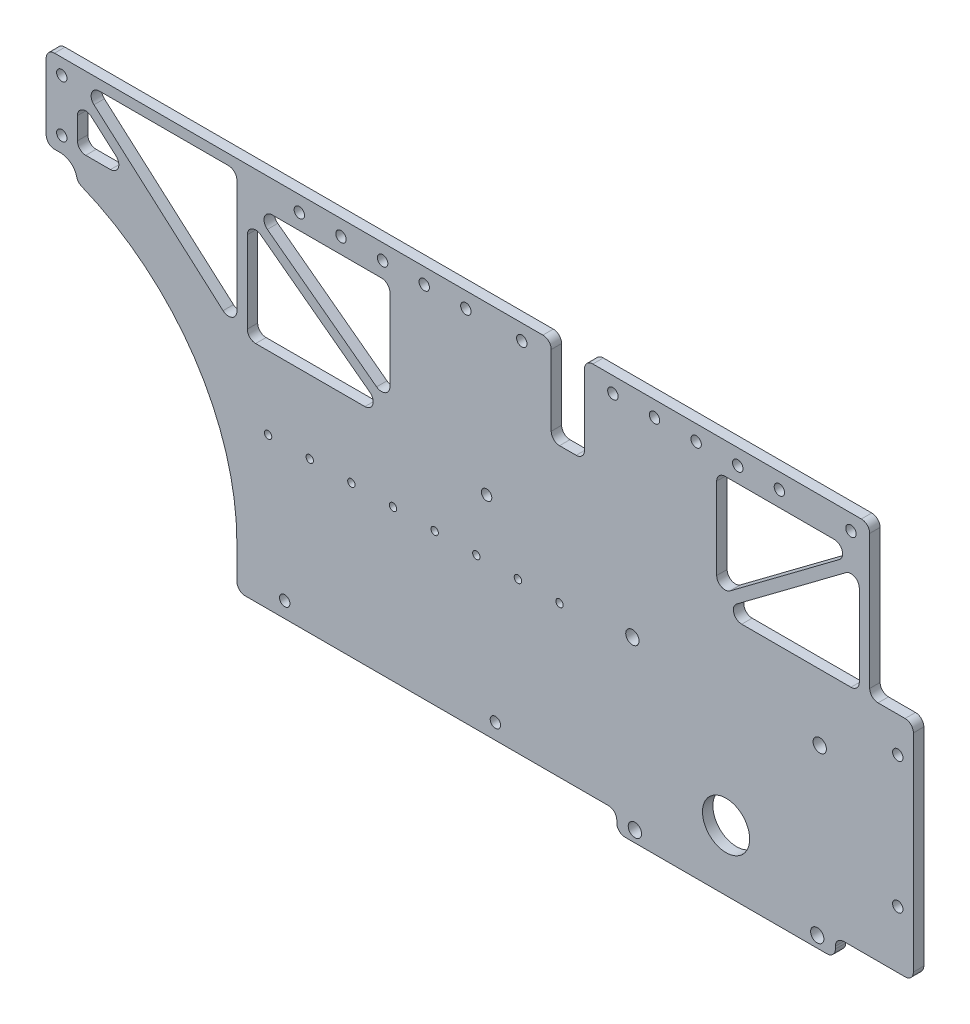
SolidWorks part; units mm, degrees
material "6061-T6 (SS)"
ref_plane "Front Plane" through (0, 0, 0) normal (0, 0, 1) x (1, 0, 0)
ref_plane "Top Plane" through (0, 0, 0) normal (0, 1, 0) x (1, 0, 0)
ref_plane "Right Plane" through (0, 0, 0) normal (1, 0, 0) x (0, 0, -1)
sketch "Sketch1" plane through (0, 0, 0) normal (0, 0, 1) x (1, 0, 0)
  line L0 (-192.2322, -144.4625) -> (49807.7678, -144.4625) construction
  line L1 (-317.5, 68.2625) -> (317.5, 68.2625)
  line L2 (-317.5, 68.2625) -> (-317.5, -68.2625)
  line L3 (-317.5, -68.2625) -> (317.5, -68.2625)
  line L4 (317.5, 68.2625) -> (317.5, -68.2625)
  line L5 (-317.5, 68.2625) -> (317.5, -68.2625) construction
  line L6 (-317.5, -68.2625) -> (317.5, 68.2625) construction
  circle A0 centre (203.2, -42.8625) radius 14.3891
  circle A1 centre (-206.8246, -42.8625) radius 14.3891
  circle A2 centre (147.5105, -73.0631) radius 4.064 construction
  circle A3 centre (258.7625, -73.0631) radius 4.064 construction
  circle A4 centre (203.2, -42.8625) radius 101.6 construction
  circle A5 centre (-206.8246, -42.8625) radius 101.6 construction
  point P0 (0, 0)
  dimension "D4" = 8.128
  dimension "D6" = 55.5625
  dimension "D7" = 203.2
  dimension "D10" = 28.7782
  dimension "D11" = 25.4
  dimension "D1" = 136.525
  dimension "D2" = 635
  dimension "D3" = 30.2006
  dimension "D5" = 111.252
  dimension "D8" = 114.3
  dimension "D9" = 410.0246
extrude "Boss-Extrude1" add sketch "Sketch1" along normal blind 6.35
sketch "Sketch2" plane through (0, 0, 6.35) normal (0, 0, 1) x (1, 0, 0)
  line L7 (-317.5, 68.2625) -> (-317.5, -68.2625) construction
  line L8 (317.5, 68.2625) -> (-317.5, 68.2625) construction
  line L16 (-186.0855, 53.0053) -> (-186.0855, -61.9125)
  line L17 (-186.0855, -61.9125) -> (-69.2582, -61.9125)
  line L18 (-69.2582, -61.9125) -> (-186.0855, 53.0053)
  line L22 (-186.0855, 61.9125) -> (-69.2582, 61.9125)
  line L23 (-69.2582, 61.9125) -> (-69.2582, -53.0053)
  line L24 (-69.2582, -53.0053) -> (-186.0855, 61.9125)
  line L25 (-66.0832, -1013.7855) -> (-66.0832, 48986.2145) construction
  line L26 (53.9191, -61.9125) -> (-62.9082, -61.9125)
  line L27 (53.9191, 53.0053) -> (53.9191, -61.9125)
  line L28 (-62.9082, -61.9125) -> (53.9191, 53.0053)
  line L29 (-62.9082, 61.9125) -> (-62.9082, -53.0053)
  line L30 (53.9191, 61.9125) -> (-62.9082, 61.9125)
  line L31 (-62.9082, -53.0053) -> (53.9191, 61.9125)
  line L32 (57.0941, -1009.4045) -> (57.0941, 48990.5955) construction
  line L33 (60.2691, 53.0053) -> (60.2691, -61.9125)
  line L34 (177.0964, -61.9125) -> (60.2691, 53.0053)
  line L35 (60.2691, -61.9125) -> (177.0964, -61.9125)
  line L36 (60.2691, 61.9125) -> (177.0964, 61.9125)
  line L37 (177.0964, -53.0053) -> (60.2691, 61.9125)
  line L38 (177.0964, 61.9125) -> (177.0964, -53.0053)
  line L43 (311.15, -23.8125) -> (257.81, -23.8125)
  line L44 (257.81, -23.8125) -> (302.577, 38.9562)
  line L47 (257.81, 61.9125) -> (257.81, -12.8766)
  line L48 (257.81, -12.8766) -> (298.7325, 44.5016)
  line L49 (251.46, 61.9125) -> (251.46, -12.8766)
  line L53 (251.46, -12.8766) -> (206.8481, 61.9125)
  line L54 (206.8481, 61.9125) -> (251.46, 61.9125)
  line L55 (203.2, -1000) -> (203.2, 49000) construction
  line L59 (0, -955.55) -> (0, 49044.45) construction
  line L60 (-1317.5, 0) -> (48682.5, 0) construction
  line L67 (311.15, 61.9125) -> (257.81, 61.9125)
  line L68 (257.81, -12.8766) -> (298.7079, 44.4672) construction
  line L71 (-317.5, -68.2625) -> (317.5, -68.2625) construction
  line L72 (-311.15, 61.9125) -> (-311.15, 55.7843) construction
  line L73 (-311.15, -61.9125) -> (-227.5637, -61.9125) construction
  line L74 (317.5, -68.2625) -> (317.5, 68.2625) construction
  line L77 (-311.15, -39.929) -> (-311.15, -61.9125) construction
  line L78 (-227.5637, -61.9125) -> (-311.15, -61.9125)
  line L79 (-311.15, -61.9125) -> (-227.5637, 51.2262)
  line L80 (-227.5637, 51.2262) -> (-227.5637, -61.9125)
  line L83 (-288.6814, -20.8137) -> (-227.5637, 61.9125)
  line L84 (-311.15, -33.3375) -> (-311.15, -51.2262)
  line L85 (-311.15, -33.3375) -> (-311.15, -43.5136) construction
  line L86 (-311.15, -13.414) -> (-311.15, 24.3572)
  line L87 (-227.5637, 61.9125) -> (-311.15, 61.9125)
  line L88 (-311.15, 61.9125) -> (-311.15, 55.7843)
  line L90 (307.1418, 56.2925) -> (311.15, 61.9125)
  line L91 (311.15, 37.8237) -> (311.15, -23.8125)
  line L92 (-311.15, 37.8237) -> (-311.15, 24.3572)
  line L93 (-311.15, 37.8237) -> (-311.15, -13.414) construction
  line L94 (-298.45, 46.804) -> (-298.45, 61.9125)
  circle A2 centre (-206.8246, -42.8625) radius 14.3891 construction
  circle A4 centre (-307.975, -33.3375) radius 3.175
  circle A6 centre (307.975, -33.3375) radius 3.175
  arc A24 (-311.15, -13.414) -> (-288.6814, -20.8137) centre (-298.6972, -13.414) ccw
  circle A30 centre (-307.975, 46.804) radius 3.175
  circle A32 centre (307.975, 46.804) radius 3.175
  circle A33 centre (307.975, 46.804) radius 3.175 construction
  arc A34 (307.1418, 56.2925) -> (298.7325, 44.5016) centre (307.975, 46.804) ccw
  arc A35 (302.577, 38.9562) -> (311.15, 37.8237) centre (307.975, 46.804) ccw
  arc A36 (-311.15, 37.8237) -> (-311.15, 55.7843) centre (-307.975, 46.804) ccw
  arc A37 (308.2866, 57.8976) -> (306.2186, 61.9125) centre (306.2186, 59.3725) ccw
  arc A38 (306.1837, 56.159) -> (307.7739, 57.1789) centre (305.706, 58.6537) ccw
  point P75 (0, 68.2625)
  point P79 (-317.5, 0)
  dimension "D7" = 6.35
  dimension "D19" = 6.35
  dimension "D20" = 6.35
  dimension "D13" = 6.35
  dimension "D21" = 53.34
  dimension "D23" = 31.75
  dimension "D30" = 6.35
  dimension "D11" = 5.08
  dimension "D14" = 6.35
  dimension "D16" = 6.35
  dimension "D3" = 6.35
  dimension "D5" = 6.35
  dimension "D6" = 6.35
  dimension "D12" = 5.08
  dimension "D18" = 6.35
  dimension "D4" = 6.35
  dimension "D8" = 6.35
  dimension "D9" = 3.175
  dimension "D10" = 3.175
  dimension "D15" = 6.35
  dimension "D17" = 6.35
extrude "Cut-Extrude1" cut sketch "Sketch2" against normal through all contours L88 A24 L83 | L80 L79 L78 | A4 | L17 L18 L16 | L24 L23 L22 | L29 L31 L30 | L38 L36 L37 | L28 L26 L27 | L33 L35 L34 | L54 L53 L49 | L67 L47 L48 | L44 L43 | A6 | A30 | A32 region at (-147.143, -23.6066, 6.35) region at (-108.2006, 23.6066, 6.35) region at (14.9767, -23.6066, 6.35) region at (-23.9657, 23.6066, 6.35) region at (99.2116, -23.6066, 6.35) region at (138.154, 23.6066, 6.35) region at (292.8925, -0.2083, 6.35) region at (275.0436, 36.6709, 6.35) region at (236.5894, 36.9828, 6.35) region at (-255.4258, -24.1996, 6.35) region at (-280.3055, 26.1513, 6.35) region at (-307.975, -33.3375, 6.35) region at (307.975, -33.3375, 6.35)
sketch "Sketch3" plane through (0, 0, 6.35) normal (0, 0, 1) x (1, 0, 0)
  line L0 (-66.0832, 68.2625) -> (-66.0832, -68.2625) construction
  line L1 (317.5, 68.2625) -> (-317.5, 68.2625) construction
  line L2 (-317.5, -68.2625) -> (317.5, -68.2625) construction
  line L3 (-69.2582, 4.4536) -> (-62.9082, 4.4536) construction
  line L4 (-69.2582, 61.9125) -> (-69.2582, -53.0053) construction
  line L5 (-62.9082, 61.9125) -> (-62.9082, -53.0053) construction
  line L6 (-206.8246, -42.8625) -> (203.2, -42.8625) construction
  line L7 (-1.8123, -1000) -> (-1.8123, 49000) construction
  line L8 (52.9336, -68.2625) -> (71.9836, -68.2625)
  line L9 (52.9336, -58.7375) -> (52.9336, -68.2625)
  line L10 (-317.5, -68.2625) -> (317.5, -68.2625) construction
  line L11 (71.9836, -58.7375) -> (71.9836, -68.2625)
  circle A0 centre (-66.0832, -58.7375) radius 3.175
  circle A1 centre (62.4586, -58.7375) radius 3.175
  arc A2 (52.9336, -58.7375) -> (71.9836, -58.7375) centre (62.4586, -58.7375) cw
  point P14 (-66.0832, 4.4536)
  point P22 (-1.8123, -42.8625)
  dimension "D1" = 6.35
  dimension "D2" = 6.35
  dimension "D3" = 6.35
extrude "Boss-Extrude5" add sketch "Sketch3<5>" against normal blind 6.35 contours A2 L9 L8 L11 A1 region at (53.203, -63.5, 6.35)
sketch "Sketch3<5>" plane through (0, 0, 6.35) normal (0, 0, 1) x (1, 0, 0) same geometry as "Sketch3"
sketch "Sketch4" plane through (0, 0, 6.35) normal (0, 0, 1) x (1, 0, 0)
  line L0 (71.9836, -61.9125) -> (177.0964, -61.9125) construction
  line L1 (0, 0) -> (50000, 0) construction
  line L10 (136.525, 61.9125) -> (269.875, 61.9125)
  line L15 (251.46, 17.6149) -> (251.46, 38.4429)
  line L23 (251.46, 38.4429) -> (269.875, 38.4429)
  line L25 (203.2, -67.2211) -> (203.2, 49932.7789) construction
  line L27 (251.46, 61.9125) -> (251.46, -12.8766) construction
  line L32 (136.525, 37.5539) -> (136.525, -79.9211)
  line L33 (136.525, -79.9211) -> (269.875, -79.9211)
  line L34 (269.875, 37.5539) -> (269.875, -79.9211)
  line L35 (206.8481, 61.9125) -> (251.46, 61.9125) construction
  line L40 (177.0964, 61.9125) -> (136.525, 61.9125)
  line L41 (177.0964, 61.9125) -> (177.0964, 17.6149)
  line L42 (177.0964, 17.6149) -> (136.525, 17.6149)
  line L43 (136.525, 61.9125) -> (136.525, 17.6149)
  line L44 (250.825, 61.9125) -> (269.875, 61.9125)
  line L46 (251.46, 17.6149) -> (269.875, 17.6149)
  line L47 (269.875, 61.9125) -> (269.875, 17.6149)
  line L49 (136.525, -61.9125) -> (269.875, -61.9125)
  line L50 (136.525, -61.9125) -> (136.525, -79.9211)
  line L51 (136.525, -79.9211) -> (269.875, -79.9211)
  line L52 (269.875, -61.9125) -> (269.875, -79.9211)
  circle A5 centre (203.2, -42.8625) radius 14.3891 construction
  circle A6 centre (147.574, -73.0631) radius 4.064
  circle A7 centre (146.05, 28.0289) radius 4.064
  circle A8 centre (258.826, -73.0631) radius 4.064
  circle A9 centre (260.35, 28.0289) radius 4.064
  point P4 (203.2, -42.8625)
  point P16 (203.2, -79.9211)
  dimension "D1" = 117.475
  dimension "D2" = 133.35
  dimension "D3" = 37.0586
  dimension "D4" = 6.858
  dimension "D5" = 11.049
  dimension "D6" = 8.128
  dimension "D7" = 6.35
  dimension "D8" = 9.525
  dimension "D9" = 6.35
  dimension "D12" = 6.35
  dimension "D10" = 9.525
  dimension "D11" = 9.525
extrude "Boss-Extrude7" add sketch "Sketch4" against normal through all contours L42 L41 L40 L32 A7 | L46 L34 L44 A9 | L49 L32 L33 L34 A6 A8 region at (157.1306, 40.1126, 6.35) region at (203.2, -70.8199, 6.35) region at (269.597, 37.9984, 6.35)
sketch "Sketch5" plane through (0, 0, 6.35) normal (0, 0, 1) x (1, 0, 0)
  circle A0 centre (146.05, 28.0289) radius 4.064
  circle A2 centre (260.35, 28.0289) radius 4.0654
  arc A3 (257.81, 24.8564) -> (257.81, 31.2014) centre (260.35, 28.0289) ccw construction
extrude "Cut-Extrude3" cut sketch "Sketch5" against normal through all
fillet "Fillet1" radius 5.08 44 edges at (-186.0855, 53.0053, 3.175) (-69.2582, -61.9125, 3.175) (-186.0855, -61.9125, 3.175) (-69.2582, 61.9125, 3.175) (-69.2582, -53.0053, 3.175) (-186.0855, 61.9125, 3.175) (-62.9082, -53.0053, 3.175) (-62.9082, 61.9125, 3.175) (53.9191, 61.9125, 3.175) (-62.9082, -61.9125, 3.175) (53.9191, 53.0053, 3.175) (60.2691, 53.0053, 3.175) (71.9836, -61.9125, 3.175) (177.0964, -61.9125, 3.175) (60.2691, 61.9125, 3.175) (177.0964, -53.0053, 3.175) (269.875, -79.9211, 3.175) (136.525, -79.9211, 3.175) (136.525, -68.2625, 3.175) (-317.5, -68.2625, 3.175) (-317.5, 68.2625, 3.175) (269.875, -68.2625, 3.175) (317.5, -68.2625, 3.175) (257.81, -23.8125, 3.175) (257.81, -12.8766, 3.175) (251.46, -12.8766, 3.175) (206.8481, 61.9125, 3.175) (136.525, 17.6149, 3.175) (177.0964, 17.6149, 3.175) (136.525, 61.9125, 3.175) (52.9336, -61.9125, 3.175) (60.2691, -49.4676, 3.175) (257.81, 61.9125, 3.175) (251.46, 61.9125, 3.175) (-227.5637, -61.9125, 3.175) (-311.15, -61.9125, 3.175) (-227.5637, 51.2262, 3.175) (-227.5637, 61.9125, 3.175) (311.15, -23.8125, 3.175) (311.15, 37.8237, 3.175) (302.577, 38.9562, 3.175) (298.7325, 44.5016, 3.175) (-311.15, 37.8237, 3.175) (-298.45, 61.9125, 3.175)
fillet "Fillet2" radius 3.175 2 edges at (257.81, 17.6149, 3.175) (257.81, 38.4429, 3.175)
extrude "Cut-Extrude4" cut sketch "Sketch3" against normal through all contours A0 | A1 | A1 region at (-66.0832, -58.7375, 6.35) region at (62.4586, -58.7375, 6.35)
fillet "Fillet4" radius 3.175 2 edges at (269.875, 17.6149, 3.175) (269.875, 38.4429, 3.175)
sketch "Sketch6" plane through (0, 0, 6.35) normal (0, 0, 1) x (1, 0, 0)
  line L1 (182.3854, 63.9908) -> (200.9425, 63.9908)
  line L2 (182.3854, 63.9908) -> (182.3854, 24.0416)
  line L3 (182.3854, 24.0416) -> (200.9425, 24.0416)
  line L4 (200.9425, 63.9908) -> (200.9425, 24.0416)
extrude "Boss-Extrude8" add sketch "Sketch6" against normal up to surface (6.35 mm away) up to face at (-62.9082, -58.7375, 0)
sketch "Sketch7" plane through (0, 0, 6.35) normal (0, 0, 1) x (1, 0, 0)
  line L0 (-317.5, 63.1825) -> (-317.5, -63.1825) construction
  line L1 (-317.5, -72.2971) -> (-95.25, -72.2971)
  line L2 (-317.5, -72.2971) -> (-317.5, 82.3764)
  line L3 (-317.5, 82.3764) -> (-95.25, 82.3764)
  line L4 (-95.25, -72.2971) -> (-95.25, 82.3764)
  dimension "D1" = 222.25
extrude "Cut-Extrude5" cut sketch "Sketch7" against normal through all
sketch "Sketch8" plane through (0, 0, 6.35) normal (0, 0, 1) x (1, 0, 0)
  line L0 (-95.25, -68.2625) -> (131.445, -68.2625) construction
  line L1 (-95.25, 68.2625) -> (-88.9, 68.2625)
  line L2 (-95.25, 68.2625) -> (-95.25, -68.2625)
  line L3 (-95.25, -68.2625) -> (-88.9, -68.2625)
  line L4 (-88.9, 68.2625) -> (-88.9, -68.2625)
  dimension "D1" = 6.35
extrude "Boss-Extrude9" add sketch "Sketch8" against normal up to surface (6.35 mm away) up to face at (-62.9082, -58.7375, 0)
fillet "Fillet5" radius 5.08 6 edges at (53.9191, -54.5182, 3.175) (-88.9, 61.9125, 3.175) (-88.9, -33.6845, 3.175) (-95.25, -68.2625, 3.175) (-88.9, -61.9125, 3.175) (-88.9, -42.5917, 3.175)
sketch "Sketch9" plane through (0, 0, 6.35) normal (0, 0, 1) x (1, 0, 0)
  line L0 (-90.17, -68.2625) -> (131.445, -68.2625) construction
  line L1 (-95.25, 68.2625) -> (317.5, 68.2625)
  line L2 (-95.25, 68.2625) -> (-95.25, 160.3375)
  line L3 (-95.25, 160.3375) -> (317.5, 160.3375)
  line L4 (317.5, 68.2625) -> (317.5, 160.3375)
  line L5 (317.5, -63.1825) -> (317.5, 68.2625) construction
  line L6 (111.125, -839.6625) -> (111.125, 49160.3375) construction
  line L11 (317.5, 68.2625) -> (290.83, 68.2625)
  line L12 (290.83, 160.3375) -> (290.83, 68.2625)
  line L13 (317.5, 160.3375) -> (290.83, 160.3375)
  line L14 (317.5, 160.3375) -> (317.5, 68.2625)
  line L15 (-88.9, 133.3567) -> (-88.9, 68.2625)
  line L16 (-88.9, 133.3567) -> (-1.905, 68.2625)
  line L17 (-1.905, 68.2625) -> (-88.9, 68.2625)
  line L18 (-88.9, 141.2875) -> (-1.905, 141.2875)
  line L19 (-1.905, 141.2875) -> (-1.905, 76.1933)
  line L20 (-1.905, 76.1933) -> (-88.9, 141.2875)
  line L21 (1.27, 160.3375) -> (1.27, 68.2625) construction
  line L40 (97.79, 160.3375) -> (97.79, 68.2625) construction
  line L47 (197.485, 141.2875) -> (197.485, 76.1933)
  line L48 (284.48, 141.2875) -> (197.485, 141.2875)
  line L49 (197.485, 76.1933) -> (284.48, 141.2875)
  line L50 (284.48, 133.3567) -> (197.485, 68.2625)
  line L51 (284.48, 133.3567) -> (284.48, 68.2625)
  line L52 (197.485, 68.2625) -> (284.48, 68.2625)
  circle A0 centre (-57.15, 150.8125) radius 3.175
  circle A2 centre (279.4, 150.8125) radius 3.175
  circle A3 centre (-31.75, 150.8125) radius 3.175
  circle A4 centre (-6.35, 150.8125) radius 3.175
  circle A5 centre (19.05, 150.8125) radius 3.175
  circle A6 centre (44.45, 150.8125) radius 3.175
  point P14 (111.125, 160.3375)
  point P17 (97.79, 114.3)
  dimension "D2" = 6.35
  dimension "D3" = 26.67
  dimension "D4" = 6.35
  dimension "D7" = 5
  dimension "D1" = 228.6
  dimension "D5" = 6.35
  dimension "D6" = 193.04
  dimension "D8" = 6.35
  dimension "D9" = 6.35
  dimension "D10" = 96.52
  dimension "D11" = 3.175
extrude "Boss-Extrude10" add sketch "Sketch9" against normal up to surface (6.35 mm away) contours L1 L12 L3 L15 L16 L47 L49 L48 L19 L20 L18 L52 L50 L51 A0 A2 region at (98.2368, 118.5001, 6.35) up to face at (-83.4975, -56.5081, 0)
sketch "Sketch10" plane through (0, 0, 6.35) normal (0, 0, 1) x (1, 0, 0)
  line L1 (53.9191, 27.649) -> (60.2691, 27.649) construction
  line L2 (53.9191, 40.8826) -> (53.9191, -53.4634) construction
  line L3 (60.2691, 40.8826) -> (60.2691, -44.4214) construction
  line L4 (41.5106, 61.9125) -> (-57.8282, 61.9125) construction
  circle A0 centre (57.0941, 58.7375) radius 3.175
  point P11 (57.0941, 27.649)
  dimension "D2" = 6.35
extrude "Cut-Extrude6" cut sketch "Sketch10" against normal through all
sketch "Sketch11" plane through (0, 0, 0) normal (0, 0, -1) x (-1, 0, 0)
  line L0 (95.25, 160.3375) -> (-290.83, 160.3375) construction
  line L1 (292.1, 160.3375) -> (95.25, 160.3375)
  line L2 (292.1, 160.3375) -> (292.1, 109.5375)
  line L3 (292.1, 109.5375) -> (95.25, 109.5375)
  line L4 (95.25, 160.3375) -> (95.25, 109.5375)
  line L5 (95.25, -63.1825) -> (95.25, 160.3375) construction
  line L6 (95.25, -63.1825) -> (95.25, 160.3375) construction
  line L8 (95.25, 109.5375) -> (95.25, -42.8625)
  line L9 (291.592, 160.3375) -> (291.592, 109.5375)
  arc A0 (247.65, 109.5375) -> (95.25, -42.8625) centre (247.65, -42.8625) ccw
  point P9 (196.85, -42.8625)
  dimension "D1" = 0.508
  dimension "D2" = 50.8
  dimension "D3" = 196.85
extrude "Boss-Extrude14" add sketch "Sketch11" against normal up to surface (6.35 mm away) contours A0 L3 L8 | L1 L4 L3 L2 region at (-193.421, 134.9375, 0) region at (-129.2913, 75.4962, 0) up to face at (60.2691, 58.7375, 6.35)
extrude "Boss-Extrude16" add sketch "Sketch2<3>" against normal up to surface (6.35 mm away) contours L29 L31 L30 | L28 L26 L27 | L54 L53 L49 | A35 L44 L43 L91 region at (14.9767, -23.6066, 6.35) region at (-23.9657, 23.6066, 6.35) region at (292.8925, -0.2083, 6.35) region at (236.5894, 36.9828, 6.35) up to face at (60.2691, 58.7375, 0)
sketch "Sketch2<3>" plane through (0, 0, 6.35) normal (0, 0, 1) x (1, 0, 0) same geometry as "Sketch2"
sketch "Sketch12" plane through (0, 0, 6.35) normal (0, 0, 1) x (1, 0, 0)
  line L0 (-69.2582, 56.8325) -> (-69.2582, -40.8826) construction
  line L1 (-88.9, 61.9125) -> (-69.2582, 61.9125)
  line L2 (-88.9, 61.9125) -> (-88.9, -46.8771)
  line L3 (-88.9, -46.8771) -> (-69.2582, -46.8771)
  line L4 (-69.2582, 61.9125) -> (-69.2582, -46.8771)
  line L5 (-88.9, -31.5558) -> (-88.9, 56.8325) construction
  line L6 (-83.82, 61.9125) -> (-74.3382, 61.9125) construction
  line L7 (136.525, 56.8325) -> (136.525, 22.6949) construction
  line L8 (60.2691, 49.0949) -> (136.525, 49.0949)
  line L9 (60.2691, 49.0949) -> (60.2691, -54.3939)
  line L10 (60.2691, -54.3939) -> (136.525, -54.3939)
  line L11 (136.525, 49.0949) -> (136.525, -54.3939)
  line L12 (60.2691, 40.8826) -> (60.2691, -44.4214) construction
  line L13 (76.9388, -61.9125) -> (164.6879, -61.9125) construction
  line L14 (66.8457, 61.9125) -> (136.525, 61.9125)
  line L15 (66.8457, 61.9125) -> (66.8457, -61.9125)
  line L16 (66.8457, -61.9125) -> (136.525, -61.9125)
  line L17 (136.525, 61.9125) -> (136.525, -61.9125)
  line L18 (72.6777, 61.9125) -> (131.445, 61.9125) construction
  line L19 (172.0164, 17.6149) -> (141.605, 17.6149) construction
  line L20 (136.525, -61.9125) -> (177.0964, -61.9125)
  line L21 (136.525, -61.9125) -> (136.525, 17.6149)
  line L22 (136.525, 17.6149) -> (177.0964, 17.6149)
  line L23 (177.0964, -61.9125) -> (177.0964, 17.6149)
  line L24 (177.0964, 12.5349) -> (177.0964, -40.8826) construction
  line L25 (257.81, 61.9125) -> (311.15, 61.9125)
  line L26 (311.15, 61.9125) -> (257.81, -12.8766)
  line L27 (257.81, -12.8766) -> (257.81, 17.6149)
  line L28 (257.81, 17.6149) -> (269.875, 17.6149)
  line L29 (269.875, 17.6149) -> (269.875, 38.4429)
  line L30 (269.875, 38.4429) -> (257.81, 38.4429)
  line L31 (257.81, 38.4429) -> (257.81, 61.9125)
  line L32 (267.0259, 0.0452) -> (297.5417, 42.832) construction
  line L33 (269.875, 35.2679) -> (269.875, 20.7899) construction
  line L34 (260.985, 17.6149) -> (266.7, 17.6149) construction
  line L35 (257.81, 14.4399) -> (257.81, 2.9949) construction
  line L36 (260.985, 38.4429) -> (266.7, 38.4429) construction
  line L37 (257.81, 56.8325) -> (257.81, 41.6179) construction
  line L39 (-91.0284, -63.1959) -> (-75.1949, -63.1959)
  line L40 (-91.0284, -63.1959) -> (-91.0284, -48.778)
  line L41 (-91.0284, -48.778) -> (-75.1949, -48.778)
  line L42 (-75.1949, -63.1959) -> (-75.1949, -48.778)
  line L43 (136.525, 17.6149) -> (141.605, 17.6149)
  line L44 (136.525, 17.6149) -> (136.525, 22.6949)
  line L45 (136.525, 22.6949) -> (141.605, 22.6949)
  line L46 (141.605, 17.6149) -> (141.605, 22.6949)
  line L47 (269.875, 38.4429) -> (266.7, 38.4429)
  line L48 (269.875, 38.4429) -> (269.875, 17.6149)
  line L49 (269.875, 17.6149) -> (266.7, 17.6149)
  line L50 (266.7, 38.4429) -> (266.7, 17.6149)
extrude "Boss-Extrude17" add sketch "Sketch12" against normal up to surface (6.35 mm away) contours L39 L42 L41 L40 | L4 L1 L2 L3 | L8 L15 L10 L17 L11 | L20 L23 L22 L17 | L17 L14 L15 L8 | L17 L10 L15 L16 | L15 L8 L9 L10 | L31 L30 L29 L28 L27 L26 L25 | L48 L47 L50 L49 | L44 L43 L46 L45 region at (-79.0791, 7.5177, 6.35) region at (63.5574, -2.6495, 6.35) region at (101.6853, 55.5037, 6.35) region at (101.6853, -2.6495, 6.35) region at (101.6853, -58.1532, 6.35) region at (156.8107, -22.1488, 6.35) region at (277.2833, 38.2734, 6.35) region at (-83.1116, -55.9869, 6.35) up to face at (60.2691, 58.7375, 0)
sketch "Sketch13" plane through (0, 0, 6.35) normal (0, 0, 1) x (1, 0, 0)
  line L0 (-95.25, 153.9875) -> (-95.25, 68.2625)
  line L1 (-95.25, 68.2625) -> (-192.5581, 153.9875)
  line L2 (-192.5581, 153.9875) -> (-95.25, 153.9875)
  line L3 (-192.5581, 145.5248) -> (-158.9162, 115.8875)
  line L4 (-291.592, 160.3375) -> (290.83, 160.3375) construction
  line L5 (-88.9, 133.3567) -> (-88.9, 68.2625) construction
  line L7 (-158.9162, 115.8875) -> (-192.5581, 115.8875)
  line L8 (-192.5581, 115.8875) -> (-192.5581, 145.5248)
  line L10 (-291.592, 109.5375) -> (-247.65, 109.5375) construction
  circle A0 centre (-202.0831, 150.8125) radius 3.175
  circle A1 centre (-202.0831, 119.0625) radius 3.175
  circle A2 centre (78.5813, 150.8125) radius 3.175
  circle A3 centre (235.7438, 150.8125) radius 3.175
  circle A4 centre (-57.15, 150.8125) radius 3.175 construction
  circle A5 centre (210.3438, 150.8125) radius 3.175
  circle A6 centre (184.9438, 150.8125) radius 3.175
  circle A7 centre (159.5438, 150.8125) radius 3.175
  circle A8 centre (134.1438, 150.8125) radius 3.175
  dimension "D6" = 6.35
  dimension "D7" = 6.35
  dimension "D8" = 6.35
  dimension "D11" = 4
  dimension "D9" = 25.4
  dimension "D4" = 6.35
  dimension "D5" = 6.35
  dimension "D1" = 6.35
  dimension "D2" = 6.35
  dimension "D3" = 6.35
  dimension "D10" = 6.35
extrude "Cut-Extrude7" cut sketch "Sketch13" against normal through all
sketch "Sketch14" plane through (0, 0, 6.35) normal (0, 0, 1) x (1, 0, 0)
  line L0 (-292.1, 109.5375) -> (-202.946, 109.5375)
  line L1 (-317.5, 109.5375) -> (-203.2, 109.5375) construction
  line L2 (-202.946, 109.5375) -> (-202.946, 102.8335)
  line L4 (-203.2, 109.5375) -> (-203.2, 103.9813) construction
  line L5 (-247.65, 109.5375) -> (-247.65, 102.8335)
  line L6 (-247.65, 102.8335) -> (-202.946, 102.8335)
  line L7 (-202.946, 102.8335) -> (-202.946, 99.2829)
  line L8 (-202.946, 99.2829) -> (-192.6914, 99.2829)
  line L9 (-291.592, 160.3375) -> (-291.592, 109.5375) construction
  arc A0 (-95.25, -42.8625) -> (-247.65, 109.5375) centre (-247.65, -42.8625) ccw construction
  arc A1 (-202.946, 109.5375) -> (-192.6914, 99.2829) centre (-202.946, 99.2829) cw
  point P13 (-203.2, 106.7594)
  dimension "D2" = 0.508
  dimension "D1" = 0.254
extrude "Cut-Extrude8" cut sketch "Sketch14" against normal through all contours L2 L0 | A1 L2 L7 L8 region at (-225.298, 106.1855, 6.35) region at (-198.5938, 103.6351, 6.35)
sketch "Sketch15" plane through (0, 0, 6.35) normal (0, 0, 1) x (1, 0, 0)
  line L0 (-291.592, 160.3375) -> (290.83, 160.3375) construction
  line L1 (96.52, 160.3375) -> (116.84, 160.3375)
  line L2 (96.52, 160.3375) -> (96.52, 106.9975)
  line L3 (96.52, 106.9975) -> (116.84, 106.9975)
  line L4 (116.84, 160.3375) -> (116.84, 106.9975)
  line L5 (317.5, -63.1825) -> (317.5, 68.2625) construction
  line L6 (-291.592, 160.3375) -> (290.83, 160.3375) construction
  line L11 (-291.592, 109.5375) -> (-211.6081, 109.5375)
  line L12 (-291.592, 109.5375) -> (-291.592, 160.3375)
  line L13 (-291.592, 160.3375) -> (-211.6081, 160.3375)
  line L14 (-211.6081, 109.5375) -> (-211.6081, 160.3375)
  circle A1 centre (-202.0831, 150.8125) radius 3.175 construction
  dimension "D1" = 53.34
  dimension "D2" = 200.66
  dimension "D3" = 220.98
  dimension "D4" = 6.35
extrude "Cut-Extrude9" cut sketch "Sketch15" against normal through all
fillet "Fillet8" radius 5.08 28 edges at (-158.9162, 115.8875, 3.175) (-192.5581, 115.8875, 3.175) (-192.5581, 145.5248, 3.175) (-95.25, 68.2625, 3.175) (-192.5581, 153.9875, 3.175) (-95.25, 153.9875, 3.175) (197.485, 68.2625, 3.175) (284.48, 133.3567, 3.175) (284.48, 68.2625, 3.175) (-88.9, 68.2625, 3.175) (-88.9, 133.3567, 3.175) (-1.905, 68.2625, 3.175) (284.48, 141.2875, 3.175) (197.485, 76.1933, 3.175) (197.485, 141.2875, 3.175) (-1.905, 76.1933, 3.175) (-88.9, 141.2875, 3.175) (-1.905, 141.2875, 3.175) (-211.6081, 109.5375, 3.175) (-192.6914, 99.2829, 3.175) (317.5, 68.2625, 3.175) (290.83, 68.2625, 3.175) (290.83, 160.3375, 3.175) (116.84, 160.3375, 3.175) (116.84, 106.9975, 3.175) (96.52, 106.9975, 3.175) (96.52, 160.3375, 3.175) (-211.6081, 160.3375, 3.175)
sketch "Sketch17" plane through (0, 0, 6.35) normal (0, 0, 1) x (1, 0, 0)
  circle A0 centre (50.8, 23.8125) radius 2.2479
  circle A1 centre (57.0941, 58.7375) radius 3.175 construction
  circle A2 centre (76.2, 23.8125) radius 2.2479
  circle A3 centre (101.6, 23.8125) radius 2.2479
  circle A19 centre (25.4, 23.8125) radius 2.2479
  circle A20 centre (0, 23.8125) radius 2.2479
  circle A21 centre (-25.4, 23.8125) radius 2.2479
  circle A22 centre (-50.8, 23.8125) radius 2.2479
  circle A23 centre (-76.2, 23.8125) radius 2.2479
  dimension "D2" = 34.925
  dimension "D3" = 4.4958
  dimension "D1" = 6.2941
  dimension "D4" = 3
  dimension "D5" = 1
  dimension "D6" = 6
extrude "Cut-Extrude10" cut sketch "Sketch17" against normal through all
